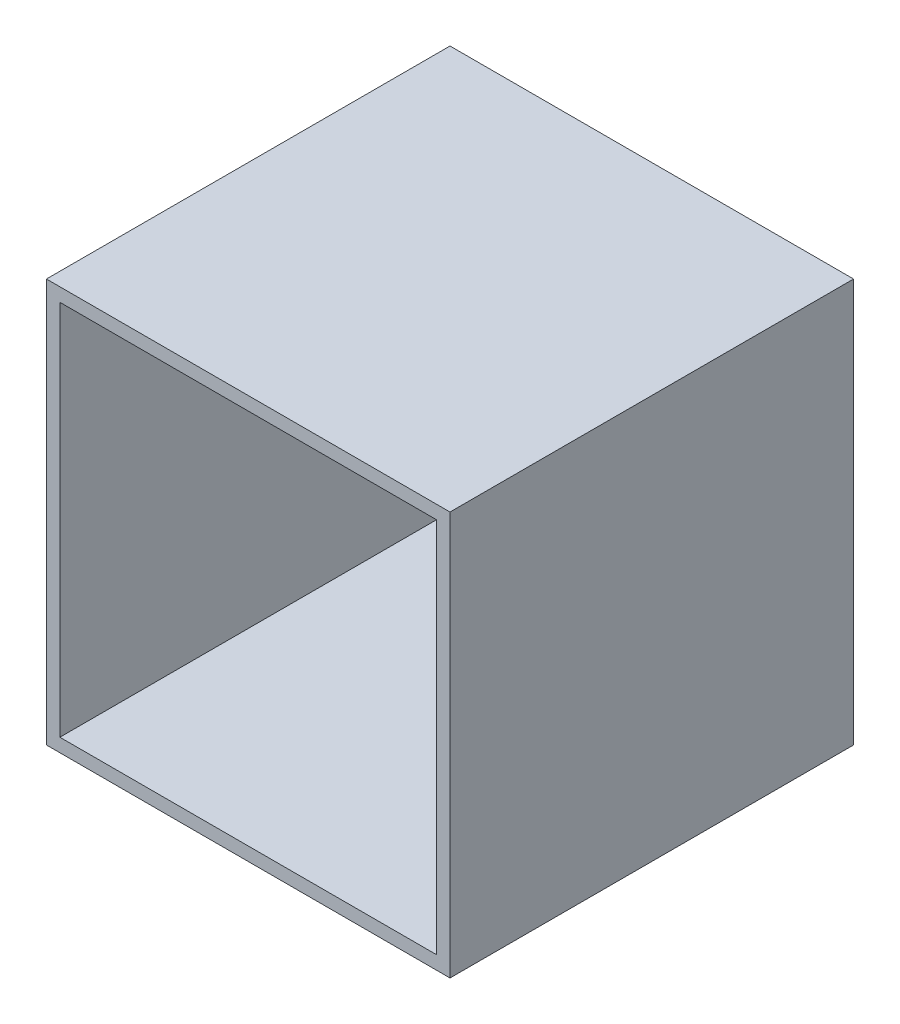
SolidWorks part; units mm, degrees
ref_plane "Front Plane" through (0, 0, 0) normal (0, 0, 1) x (1, 0, 0)
ref_plane "Top Plane" through (0, 0, 0) normal (0, 1, 0) x (1, 0, 0)
ref_plane "Right Plane" through (0, 0, 0) normal (1, 0, 0) x (0, 0, -1)
sketch "Sketch1" plane through (0, 0, 0) normal (0, 1, 0) x (1, 0, 0)
  line L1 (-38.1, -38.1) -> (38.1, -38.1)
  line L2 (-38.1, -38.1) -> (-38.1, 38.1)
  line L3 (-38.1, 38.1) -> (38.1, 38.1)
  line L4 (38.1, -38.1) -> (38.1, 38.1)
  line L5 (-38.1, -38.1) -> (38.1, 38.1) construction
  line L6 (-38.1, 38.1) -> (38.1, -38.1) construction
  point P0 (0, 0)
  dimension "D1" = 76.2
  dimension "D2" = 76.2
extrude "box" add sketch "Sketch1" along normal blind 76.2
shell "hollow it" thickness 2.54 removed face at (0, 38.1, 38.1)
sketch "Sketch2" plane through (0, 0, -38.1) normal (0, 0, -1) x (-1, 0, 0)
  line L0 (-38.1, 76.2) -> (38.1, 76.2) construction
  line L1 (-31.75, 69.85) -> (-24.13, 69.85)
  line L2 (-31.75, 69.85) -> (-31.75, 6.35)
  line L3 (-31.75, 6.35) -> (-24.13, 6.35)
  line L4 (-24.13, 69.85) -> (-24.13, 6.35)
  line L6 (-38.1, 76.2) -> (-38.1, 0) construction
  dimension "D1" = 7.62
  dimension "D2" = 63.5
  dimension "D3" = 6.35
  dimension "D4" = 6.35
extrude "slider track" cut sketch "Sketch2" against normal up to surface (2.54 mm away) up to face at (0, 38.1, -35.56)
sketch "Sketch4" plane through (0, 0, -38.1) normal (0, 0, -1) x (-1, 0, 0)
  line L0 (-38.1, 76.2) -> (38.1, 76.2) construction
  circle A0 centre (0, 63.5) radius 6.35
  dimension "D1" = 12.7
  dimension "D2" = 12.7
extrude "button large ring" cut sketch "Sketch4" against normal blind 1.27
sketch "Sketch5" plane through (0, 0, -36.83) normal (0, 0, -1) x (-1, 0, 0)
  circle A0 centre (0, 63.5) radius 3.556
  circle A1 centre (0, 63.5) radius 6.35 construction
  dimension "D2" = 7.112
  dimension "D1" = 0
extrude "button small hole" cut sketch "Sketch5" against normal blind 1.27
sketch "Sketch6" plane through (0, 0, -38.1) normal (0, 0, -1) x (-1, 0, 0)
  line L0 (-3.2977, 45.72) -> (-3.2977, 52.07)
  line L1 (-3.2977, 52.07) -> (3.0523, 52.07)
  line L2 (3.0523, 52.07) -> (3.0523, 45.72)
  line L3 (3.0523, 45.72) -> (9.4023, 45.72)
  line L4 (9.4023, 45.72) -> (9.4023, 39.37)
  line L5 (9.4023, 39.37) -> (3.0523, 39.37)
  line L6 (3.0523, 39.37) -> (3.0523, 33.02)
  line L7 (3.0523, 33.02) -> (-3.2977, 33.02)
  line L8 (-3.2977, 33.02) -> (-3.2977, 39.37)
  line L9 (-3.2977, 39.37) -> (-9.6477, 39.37)
  line L10 (-9.6477, 39.37) -> (-9.6477, 45.72)
  line L11 (-9.6477, 45.72) -> (-3.2977, 45.72)
  line L12 (-38.1, 0) -> (38.1, 0) construction
  dimension "D1" = 6.35
  dimension "D2" = 6.35
  dimension "D3" = 6.35
  dimension "D4" = 6.35
  dimension "D5" = 6.35
  dimension "D6" = 6.35
  dimension "D7" = 6.35
  dimension "D8" = 6.35
  dimension "D9" = 6.35
  dimension "D10" = 33.02
extrude "dpad large shape" cut sketch "Sketch6" against normal blind 1.27
sketch "Sketch7" plane through (0, 0, -36.83) normal (0, 0, -1) x (-1, 0, 0)
  line L0 (-3.2977, 45.72) -> (-9.6477, 45.72) construction
  line L1 (-9.6477, 45.72) -> (-9.6477, 39.37) construction
  line L2 (3.0523, 33.02) -> (3.0523, 39.37) construction
  line L3 (-3.2977, 33.02) -> (3.0523, 33.02) construction
  line L4 (3.0523, 39.37) -> (9.4023, 39.37) construction
  line L5 (9.4023, 39.37) -> (9.4023, 45.72) construction
  line L6 (3.0523, 45.72) -> (3.0523, 52.07) construction
  line L7 (-3.2977, 52.07) -> (-3.2977, 45.72) construction
  line L8 (3.0523, 52.07) -> (-3.2977, 52.07) construction
  circle A0 centre (-0.1227, 48.895) radius 1.397
  circle A1 centre (6.2273, 42.545) radius 1.397
  circle A2 centre (-0.1227, 36.195) radius 1.397
  circle A3 centre (-6.4727, 42.545) radius 1.397
  point P12 (3.0523, 36.195)
  point P17 (6.2273, 39.37)
  dimension "D3" = 2.794
  dimension "D6" = 2.794
  dimension "D9" = 2.794
  dimension "D13" = 2.794
  dimension "D1" = 3.175
  dimension "D2" = 3.175
  dimension "D4" = 3.175
  dimension "D5" = 3.175
  dimension "D7" = 3.175
  dimension "D8" = 3.175
  dimension "D10" = 3.175
  dimension "D11" = 3.175
  dimension "D12" = 3.175
extrude "dpad tiny holes" cut sketch "Sketch7" against normal blind 1.27
sketch "Sketch8" plane through (0, 0, -38.1) normal (0, 0, -1) x (-1, 0, 0)
  line L0 (38.1, 76.2) -> (38.1, 0) construction
  line L1 (-38.1, 76.2) -> (38.1, 76.2) construction
  circle A0 centre (20.32, 19.05) radius 12.7
  dimension "D1" = 25.4
  dimension "D2" = 17.78
  dimension "D3" = 57.15
extrude "dial large ring" cut sketch "Sketch8" against normal blind 1.27
ref_point "dial center"
sketch "Sketch9" plane through (0, 0, -36.83) normal (0, 0, -1) x (-1, 0, 0)
  circle A0 centre (20.32, 19.05) radius 5.08
  dimension "D1" = 10.16
extrude "dial small hole" cut sketch "Sketch9" against normal blind 1.27
sketch "Sketch10" plane through (0, 73.66, 0) normal (0, -1, 0) x (1, 0, 0)
  line L0 (35.56, -35.56) -> (-35.56, -35.56) construction
  line L1 (-35.56, -35.56) -> (-35.56, 38.1) construction
  circle A0 centre (-12.7, -13.563) radius 3.81
  point P2 (0, -35.56)
  dimension "D1" = 25.4
  dimension "D2" = 22.86
extrude "obstruction for baton" add sketch "Sketch10" along normal blind 12.7
sketch "Sketch12" plane through (0, 0, -38.1) normal (0, 0, -1) x (-1, 0, 0)
  line L0 (38.1, 76.2) -> (38.1, 0) construction
  line L1 (-13.97, 30.48) -> (-2.54, 30.48)
  line L2 (-13.97, 30.48) -> (-13.97, 5.08)
  line L3 (-13.97, 5.08) -> (-2.54, 5.08)
  line L4 (-2.54, 30.48) -> (-2.54, 5.08)
  line L5 (-38.1, 0) -> (38.1, 0) construction
  dimension "D1" = 25.4
  dimension "D2" = 11.43
  dimension "D3" = 40.64
  dimension "D4" = 5.08
extrude "hole for scroll wheel" cut sketch "Sketch12" against normal blind 2.54
sketch "Sketch14" plane through (2.54, 0, 0) normal (1, 0, 0) x (0, 0, -1)
  line L0 (38.1, 5.08) -> (38.1, 30.48) construction
  circle A0 centre (38.1, 17.78) radius 6.35
extrude "nibble base 1" add sketch "Sketch14" against normal blind 5.08
sketch "Sketch15" plane through (13.97, 0, 0) normal (-1, 0, 0) x (0, 0, 1)
  line L0 (-38.1, 30.48) -> (-38.1, 5.08) construction
  circle A0 centre (-38.1, 17.78) radius 6.35
extrude "nibble base 2" add sketch "Sketch15" against normal blind 5.08
sketch "Sketch16" plane through (13.97, 0, 0) normal (-1, 0, 0) x (0, 0, 1)
  circle A0 centre (-38.1, 17.78) radius 3.81
extrude "nibble holes" cut sketch "Sketch16" against normal up to surface and the other way up to surface up to face at (19.05, 17.78, -41.275) other way up to face at (-2.54, 17.78, -41.275)
